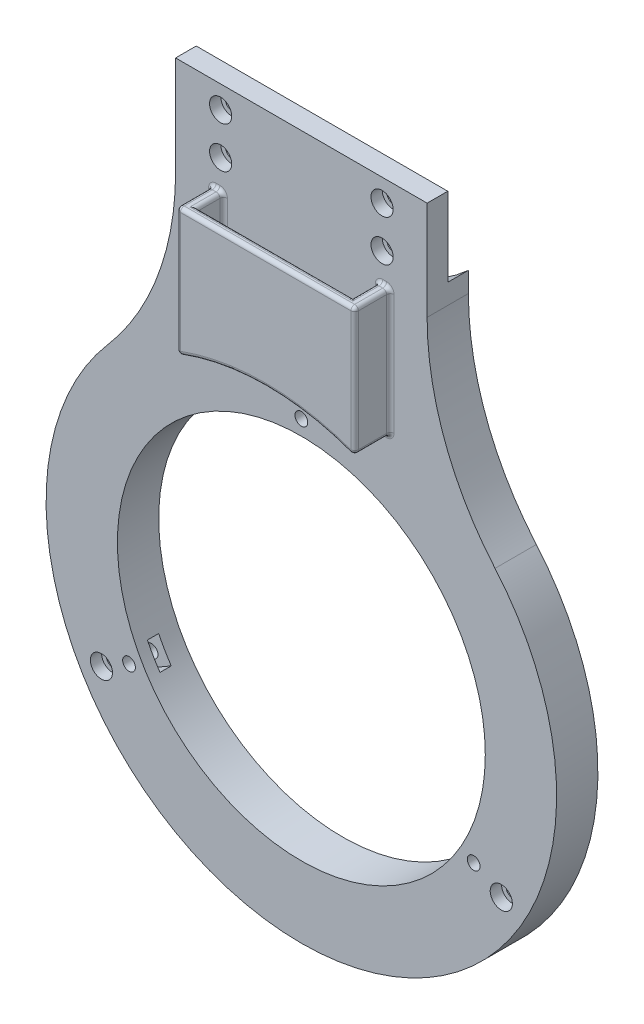
SolidWorks part; units mm, degrees
ref_plane "Front Plane" through (0, 0, 0) normal (0, 0, 1) x (1, 0, 0)
ref_plane "Top Plane" through (0, 0, 0) normal (0, 1, 0) x (1, 0, 0)
ref_plane "Right Plane" through (0, 0, 0) normal (1, 0, 0) x (0, 0, -1)
sketch "Sketch1" plane through (0, 0, 0) normal (0, 0, 1) x (1, 0, 0)
  circle A0 centre (0, 0) radius 68
  circle A1 centre (0, 0) radius 49
  dimension "D1" = 136
  dimension "D2" = 98
extrude "Boss-Extrude1" add sketch "Sketch1" along normal blind 5.5 and the other way blind 5.5
sketch "Sketch2" plane through (0, 0, -5.5) normal (0, 0, -1) x (-1, 0, 0)
  line L0 (-76.2552, 0) -> (83.6012, 0) construction
  line L1 (-21.5, 119.5) -> (21.5, 119.5)
  line L2 (-21.5, 119.5) -> (-21.5, 76.5)
  line L3 (-21.5, 76.5) -> (21.5, 76.5)
  line L4 (21.5, 119.5) -> (21.5, 76.5)
  line L5 (-21.5, 119.5) -> (21.5, 76.5) construction
  line L6 (-21.5, 76.5) -> (21.5, 119.5) construction
  line L7 (-33.5, 119.5) -> (33.5, 119.5)
  line L8 (-33.5, 119.5) -> (-33.5, 66.5)
  line L9 (-33.5, 66.5) -> (33.5, 66.5)
  line L10 (33.5, 119.5) -> (33.5, 66.5)
  line L11 (-33.5, 119.5) -> (33.5, 66.5) construction
  line L12 (-33.5, 66.5) -> (33.5, 119.5) construction
  line L13 (-59.5091, 98) -> (49.588, 98) construction
  line L14 (0, 0) -> (-73.46, 73.46) construction
  line L15 (0, 0) -> (0, 98) construction
  line L16 (0, 0) -> (73.46, 73.46) construction
  line L17 (-51.5944, 44.2947) -> (51.5944, 44.2947)
  circle A0 centre (-33.5, 98) radius 2.5982 construction
  circle A1 centre (-48.0833, 48.0833) radius 10.7942 construction
  circle A2 centre (0, 0) radius 68 construction
  circle A3 centre (48.0833, 48.0833) radius 10.7942 construction
  circle A4 centre (33.5, 98) radius 2.5982 construction
  arc A5 (-51.5944, 44.2947) -> (-33.5, 93.1491) centre (-108.5, 93.1491) ccw
  circle A6 centre (-0.7791, 0.7791) radius 34.0704
  circle A7 centre (0, 0) radius 68 construction
  arc A8 (51.5944, 44.2947) -> (33.5, 93.1491) centre (108.5, 93.1491) cw
  circle A9 centre (0, 98) radius 18.5
  point P0 (0, 98)
  point P5 (0, 93)
  circle M5 centre (0, 0) radius 49
  circle M6 centre (0, 0) radius 68
  dimension "D8" = 136
  dimension "D9" = 75
  dimension "D5" = 37
  dimension "D1" = 43
  dimension "D2" = 43
  dimension "D3" = 76.5
  dimension "D4" = 12
  dimension "D6" = 10
  dimension "D7" = 45
extrude "Boss-Extrude2" add sketch "Sketch2" against normal blind 11 contours A5 L9 L8 M6 | L17 L9 M6 M5 | A8 L10 L9 M6 | L9 M6 | L10 L7 L4 L3 L2 L8 L9 M6 | L4 L1 L2 L3 A9 | A9 region at (0, 118.8919, -5.5) region at (22.3543, 98, -5.5) region at (34.377, 64.0659, -5.5) region at (-34.377, 64.0659, -5.5) region at (0, 54.3602, -5.5) region at (0, 67.1006, -5.5) region at (0, 98, -5.5)
sketch "Sketch3" plane through (0, 0, 5.5) normal (0, 0, 1) x (1, 0, 0)
  line L0 (-33.5, 119.5) -> (33.5, 119.5)
  line L1 (-33.5, 119.5) -> (-33.5, 98.5)
  line L2 (33.5, 119.5) -> (33.5, 98.5)
  line L3 (-33.5, 98.5) -> (33.5, 98.5)
  line L4 (0, 119.5) -> (0, 98.5) construction
  circle A0 centre (-21.5, 113.5) radius 1.7
  circle A2 centre (-21.5, 102.5) radius 1.7
  circle A3 centre (-21.5, 102.5) radius 2.95
  circle A4 centre (-21.5, 113.5) radius 2.95
  circle A5 centre (21.5, 113.5) radius 2.95
  circle A6 centre (21.5, 102.5) radius 2.95
  circle A7 centre (21.5, 102.5) radius 1.7
  circle A8 centre (21.5, 113.5) radius 1.7
  dimension "D3" = 3.4
  dimension "D4" = 3.4
  dimension "D8" = 5.9
  dimension "D9" = 5.9
  dimension "D1" = 21
  dimension "D2" = 6
  dimension "D5" = 12
  dimension "D6" = 12
  dimension "D7" = 11
  dimension "D10" = 33.5
  dimension "D11" = 33.5
extrude "Cut-Extrude1" cut sketch "Sketch3" against normal through all contours A0 | A2 | A8 | A7 region at (-21.5, 113.5, 5.5) region at (-21.5, 102.5, 5.5)
sketch "Sketch4" plane through (0, 0, 5.5) normal (0, 0, 1) x (1, 0, 0)
  circle A0 centre (-21.5, 113.5) radius 2.95
  circle A1 centre (-21.5, 102.5) radius 2.95
  circle A2 centre (21.5, 102.5) radius 2.95
  circle A3 centre (21.5, 113.5) radius 2.95
  dimension "D1" = 5.9
  dimension "D2" = 5.9
  dimension "D3" = 5.9
  dimension "D4" = 5.9
extrude "Cut-Extrude2" cut sketch "Sketch4" against normal blind 3 contours A0 | A3 | A2 | A1
sketch "Sketch5" plane through (0, 0, -5.5) normal (0, 0, -1) x (-1, 0, 0)
  line L0 (-33.5, 119.5) -> (33.5, 119.5)
  line L1 (-33.5, 119.5) -> (-33.5, 98.5)
  line L2 (33.5, 119.5) -> (33.5, 98.5)
  line L3 (-33.5, 98.5) -> (33.5, 98.5)
  circle A0 centre (0, 135.6181) radius 50
  circle M6 centre (21.5, 102.5) radius 1.7
  circle M7 centre (21.5, 113.5) radius 1.7
  line M11 (33.5, 93.1491) -> (33.5, 119.5)
  line M12 (33.5, 119.5) -> (-33.5, 119.5)
  line M13 (-33.5, 119.5) -> (-33.5, 93.1491)
  circle M15 centre (-21.5, 102.5) radius 1.7
  circle M16 centre (-21.5, 113.5) radius 1.7
  dimension "D2" = 100
  dimension "D1" = 21
extrude "Cut-Extrude3" cut sketch "Sketch5" against normal blind 5.5 contours L3 M13 M11 M12 M6 M15 M16 M7 | L3 A0 region at (0, 109.0265, -5.5) region at (0, 93.2857, -5.5)
sketch "Sketch6" plane through (0, 0, -5.5) normal (0, 0, -1) x (-1, 0, 0)
  circle A0 centre (0, 0) radius 61.5 construction
  circle A1 centre (0, 61.5) radius 1.7
  circle A2 centre (53.2606, -30.75) radius 1.7
  circle A3 centre (-53.2606, -30.75) radius 1.7
  point P12 (0, 0)
  dimension "D1" = 123
  dimension "D2" = 3.4
  dimension "D3" = 3
extrude "Cut-Extrude4" cut sketch "Sketch6" against normal through all
sketch "Sketch7" plane through (0, 0, -5.5) normal (0, 0, -1) x (-1, 0, 0)
  line L8 (0, 0) -> (0, 53) construction
  circle A0 centre (0, 0) radius 53 construction
  circle A1 centre (0, 53) radius 1.7
  point P12 (0, 0)
  dimension "D2" = 106
  dimension "D3" = 3.4
extrude "Cut-Extrude5" cut sketch "Sketch7" against normal through all
pattern_circular "CirPattern1" count 3 over 360 about axis through (0, 0, -5.5) along (0, 0, 1) of "Cut-Extrude5"
ref_plane "Plane1" through (0, 0, 2.5) normal (0, 0, 1) x (1, 0, 0)
sketch "Sketch8" plane through (0, 0, 2.5) normal (0, 0, 1) x (1, 0, 0)
  line L0 (-3.35, 53) -> (3.35, 53) construction
  line L1 (-1.675, 55.9012) -> (1.675, 50.0988) construction
  line L2 (-1.675, 50.0988) -> (1.675, 55.9012) construction
  line L3 (-1.675, 55.9012) -> (1.675, 55.9012)
  line L4 (1.675, 55.9012) -> (3.35, 53)
  line L5 (3.35, 53) -> (1.675, 50.0988)
  line L6 (1.675, 50.0988) -> (-1.675, 50.0988)
  line L7 (-1.675, 50.0988) -> (-3.35, 53)
  line L8 (-3.35, 53) -> (-1.675, 55.9012)
  line L9 (-3.35, 53) -> (-3.35, 47.3469)
  line L10 (-3.35, 47.3469) -> (3.35, 47.3469)
  line L11 (3.35, 47.3469) -> (3.35, 53)
  circle A0 centre (0, 53) radius 3.35 construction
  circle A2 centre (0, 53) radius 1.7 construction
  circle A3 centre (0, 53) radius 1.7 construction
  dimension "D1" = 6.7
  dimension "D4" = 3.4
  dimension "D2" = 60
  dimension "D3" = 60
  dimension "D5" = 5.6531
  dimension "D6" = 53
extrude "Cut-Extrude6" cut sketch "Sketch8" against normal blind 3 contours L10 L11 L5 L6 L7 L9 | L8 L7 L6 L5 L4 L3 region at (0, 53, 2.5) region at (0, 49.2116, 2.5)
pattern_circular "CirPattern2" count 3 over 360 about axis through (0, 0, 5.5) along (0, 0, 1) of "Cut-Extrude6"
sketch "Sketch10" plane through (0, 0, 5.5) normal (0, 0, 1) x (1, 0, 0)
  circle A0 centre (0, 61.5) radius 2.95
  dimension "D1" = 5.9
extrude "Cut-Extrude8" cut sketch "Sketch10" against normal blind 3
pattern_circular "CirPattern4" count 3 over 360 about axis through (0, 0, 5.5) along (0, 0, 1) of "Cut-Extrude8"
sketch "Sketch13" plane through (0, 0, 5.5) normal (0, 0, 1) x (1, 0, 0)
  line L0 (-23.7, 0) -> (-23.7, 95)
  line L1 (-23.7, 95) -> (23.7, 95)
  line L2 (23.7, 95) -> (23.7, 0)
  circle A0 centre (0, 0) radius 65
  circle A1 centre (0, 0) radius 23.7
  dimension "D1" = 130
  dimension "D2" = 47.4
  dimension "D4" = 95
extrude "Boss-Extrude4" add sketch "Sketch13" along normal blind 9.5 contours A0 L2 L1 L0 region at (0, 79.2368, 5.5)
sketch "Sketch14" plane through (0, 95, 0) normal (0, 1, 0) x (1, 0, 0)
  line L0 (33.5, -5.5) -> (-33.5, -5.5) construction
  line L1 (-20.7, -5.5) -> (20.7, -5.5)
  line L2 (-20.7, -5.5) -> (-20.7, -12.5)
  line L3 (-20.7, -12.5) -> (20.7, -12.5)
  line L4 (20.7, -5.5) -> (20.7, -12.5)
  line L5 (-23.7, -15) -> (23.7, -15) construction
  line L6 (23.7, -15) -> (23.7, -5.5) construction
  line L7 (-23.7, -15) -> (-23.7, -5.5) construction
  dimension "D1" = 2.5
  dimension "D2" = 3
  dimension "D3" = 3
extrude "Cut-Extrude10" cut sketch "Sketch14" against normal through all
fillet "Fillet2" radius 1 22 edges at (23.7, 77.7626, 5.5) (-20.7, 78.3079, 5.5) (22.2067, 61.089, 5.5) (22.2, 95, 5.5) (-22.2067, 61.089, 5.5) (-22.2, 95, 5.5) (20.7, 78.3079, 5.5) (-23.7, 77.7626, 5.5) (20.7, 61.6158, 9) (-20.7, 61.6158, 9) (0, 65, 12.5) (0, 95, 15) (23.7, 95, 10.25) (20.7, 95, 9) (0, 95, 12.5) (-20.7, 95, 9) (-23.7, 95, 10.25) (-23.7, 60.5253, 10.25) (0, 65, 15) (23.7, 60.5253, 10.25) (23.7, 77.7626, 15) (-23.7, 77.7626, 15)
equation "\"D3@Sketch2\"=68+(60/2)-(43/2)"
